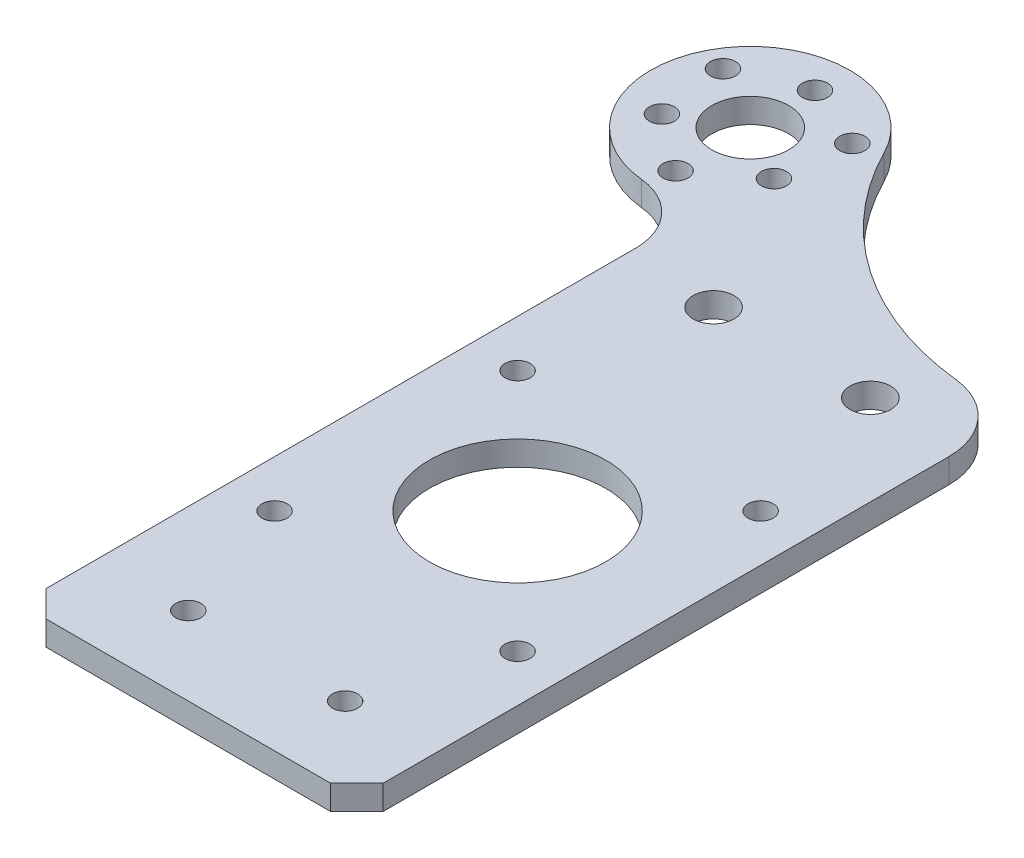
SolidWorks part; units mm, degrees
material "6061-T6 (SS)"
ref_plane "Front Plane" through (0, 0, 0) normal (0, 0, 1) x (1, 0, 0)
ref_plane "Top Plane" through (0, 0, 0) normal (0, 1, 0) x (1, 0, 0)
ref_plane "Right Plane" through (0, 0, 0) normal (1, 0, 0) x (0, 0, -1)
sketch "Sketch1" plane through (0, 0, 0) normal (0, 1, 0) x (1, 0, 0)
  line L0 (-27.5, 86.48) -> (-21.5, 86.48)
  line L1 (-21.5, 3.35) -> (-18.15, 0)
  line L2 (15.5, 57.5) -> (-15.5, 57.5) construction
  line L3 (15.5, 57.5) -> (15.5, 26.5) construction
  line L4 (15.5, 26.5) -> (-15.5, 26.5) construction
  line L5 (-15.5, 57.5) -> (-15.5, 26.5) construction
  line L6 (15.5, 57.5) -> (-15.5, 26.5) construction
  line L7 (15.5, 26.5) -> (-15.5, 57.5) construction
  line L8 (18.15, 0) -> (21.5, 3.35)
  line L193 (0, 0) -> (0, 88.5481) construction
  line L241 (21.5, 75.5175) -> (21.5, 3.35)
  line L244 (-18.15, 0) -> (18.15, 0)
  line L255 (-21.5, 86.48) -> (-21.5, 3.35)
  circle A0 centre (-27.5, 99.18) radius 4.9
  arc A1 (-16.1735, 104.9246) -> (13.4614, 84.466) centre (17.4939, 122) ccw
  circle A2 centre (-27.5, 99.18) radius 8.25 construction
  circle A3 centre (10, 77) radius 2.6
  circle A4 centre (-10, 77) radius 2.6
  circle A5 centre (10, 10) radius 1.6
  circle A6 centre (-10, 10) radius 1.6
  circle A7 centre (-20.3553, 95.055) radius 1.6
  circle A8 centre (-34.6447, 95.055) radius 1.6
  circle A9 centre (-27.5, 107.43) radius 1.6
  arc A10 (-16.1735, 104.9246) -> (-27.5, 86.48) centre (-27.5, 99.18) ccw
  circle A11 centre (0, 42) radius 11.25
  circle A12 centre (-15.5, 26.5) radius 1.6
  circle A13 centre (-15.5, 57.5) radius 1.6
  circle A14 centre (15.5, 57.5) radius 1.6
  circle A15 centre (15.5, 26.5) radius 1.6
  arc A16 (13.4614, 84.466) -> (21.5, 75.5175) centre (12.5, 75.5175) cw
  point P15 (21.5, 0)
  point P16 (-21.5, 0)
  point P24 (0, 42)
  point P30 (-27.5, 99.18)
  dimension "D5" = 20
  dimension "D6" = 10
  dimension "D7" = 5.2
  dimension "D8" = 77
  dimension "D9" = 20
  dimension "D10" = 25.4
  dimension "D12" = 122
  dimension "D13" = 37.75
  dimension "D15" = 31
  dimension "D4" = 42
  dimension "D2" = 3.2
  dimension "D17" = 22.5
  dimension "D18" = 3
  dimension "D11" = 22.18
  dimension "D19" = 9.8
  dimension "D20" = 16.5
  dimension "D21" = 9
  dimension "D3" = 4
  dimension "D14" = 27.5
  dimension "D16" = 43
  dimension "D22" = 3.35
  dimension "D23" = 3.35
  dimension "D24" = 3.35
  dimension "D25" = 3.35
extrude "Boss-Extrude1" add sketch "Sketch1" along normal blind 3.125
sketch "Sketch2" plane through (0, 3.125, 0) normal (0, 1, 0) x (1, 0, 0)
  line L0 (10, 77) -> (-10, 77) construction
  line L2 (-31.1681, 59.8462) -> (-31.4022, 59.8708) construction
ref_plane "Plane1" through (0, 0, -77) normal (0, 0, -1) x (-1, 0, 0)
fillet "Fillet1" radius 8 1 edges at (-21.5, 1.5625, -86.48)
sketch "Sketch3" plane through (0, 3.125, 0) normal (0, 1, 0) x (1, 0, 0)
  circle A0 centre (-27.5, 99.18) radius 9.5263 construction
  circle A1 centre (-27.5, 89.6537) radius 1.6
  circle A2 centre (-35.75, 103.9431) radius 1.6
  circle A3 centre (-19.25, 103.9431) radius 1.6
  point P12 (-27.5, 99.18)
  dimension "D1" = 3.2
  dimension "D3" = 16.5
  dimension "D2" = 3
extrude "Cut-Extrude1" cut sketch "Sketch3" against normal up to next
equation "\"D23@Sketch1\"=\"D22@Sketch1\""
equation "\"D24@Sketch1\"=\"D22@Sketch1\""
equation "\"D25@Sketch1\"=\"D22@Sketch1\""
